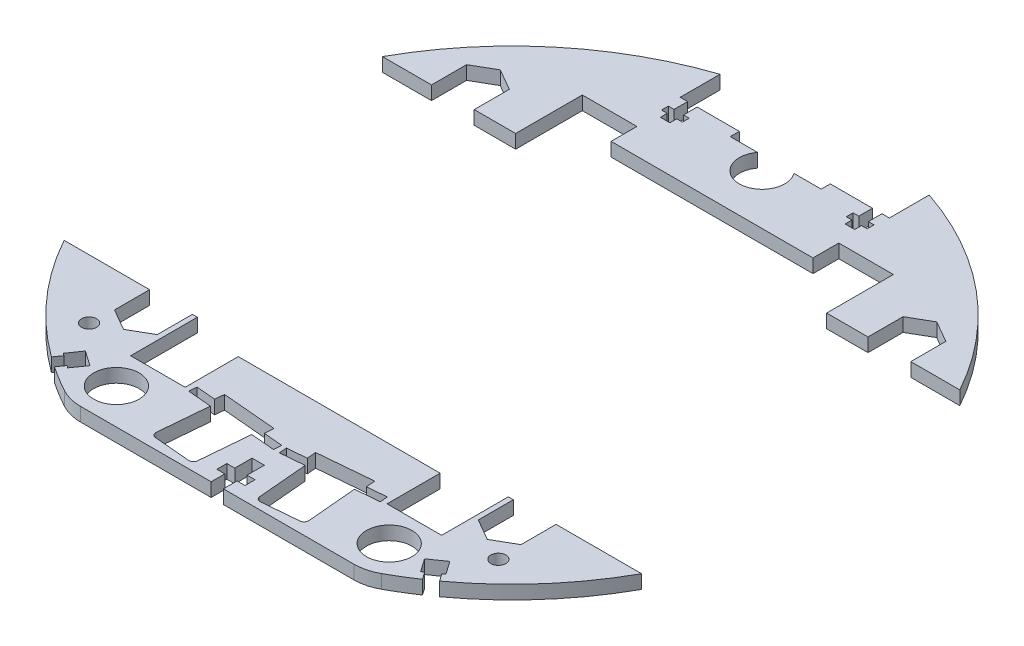
SolidWorks part; units mm, degrees
ref_plane "Front Plane" through (0, 0, 0) normal (0, 0, 1) x (1, 0, 0)
ref_plane "Top Plane" through (0, 0, 0) normal (0, 1, 0) x (1, 0, 0)
ref_plane "Right Plane" through (0, 0, 0) normal (1, 0, 0) x (0, 0, -1)
sketch "Sketch1" plane through (0, 0, 0) normal (0, 1, 0) x (1, 0, 0)
  line L0 (-30.03, -64.8129) -> (30.03, -64.8129)
  line L1 (0, -85) -> (0, 0) construction
  line L2 (0, -85) -> (32.4891, -64.8129) construction
  arc A0 (34.8348, -63.5829) -> (-34.8348, -63.5829) centre (0, 0) ccw
  circle A1 centre (0, -85) radius 38.25 construction
  arc A2 (30.03, -64.8129) -> (34.8348, -63.5829) centre (30.03, -54.8129) ccw
  arc A3 (-30.03, -64.8129) -> (-34.8348, -63.5829) centre (-30.03, -54.8129) cw
  dimension "D1" = 145
  dimension "D2" = 76.5
  dimension "D4" = 10
  dimension "D3" = 85
extrude "Boss-Extrude1" add sketch "Sketch1" along normal blind 3
sketch "Sketch2" plane through (0, 3, 0) normal (0, 1, 0) x (1, 0, 0)
  line L29 (-22.2, -49.6757) -> (-22.2, -32.5) construction
  line L30 (-22.2, -49.6757) -> (-22.2, -32.5) construction
  line L38 (-34.2, -49.6757) -> (-22.2, -49.6757) construction
  line L39 (-34.2, -49.6757) -> (-34.2, 49.6757) construction
  line L40 (-34.2, 49.6757) -> (-22.2, 49.6757) construction
  line L41 (-22.2, 32.5) -> (-22.2, 49.6757) construction
  line L47 (22.2, 32.5) -> (22.2, 49.6757) construction
  line L48 (34.2, 49.6757) -> (22.2, 49.6757) construction
  line L49 (34.2, -49.6757) -> (34.2, 49.6757) construction
  line L50 (34.2, -49.6757) -> (22.2, -49.6757) construction
  line L51 (22.2, -49.6757) -> (22.2, -32.5) construction
  line L52 (22.2, -49.6757) -> (22.2, -32.5) construction
  line L53 (-22.2, -49.6757) -> (-22.2, -38) construction
  line L54 (-22.2, -49.6757) -> (-22.2, -38)
  line L55 (-22.2, 44) -> (22.2, 44)
  line L62 (-34.2, -49.6757) -> (-22.2, -49.6757)
  line L63 (-34.2, -49.6757) -> (-34.2, 49.6757)
  line L64 (-34.2, 49.6757) -> (-22.2, 49.6757)
  line L65 (-22.2, 44) -> (-22.2, 49.6757)
  line L71 (22.2, 44) -> (22.2, 49.6757)
  line L72 (34.2, 49.6757) -> (22.2, 49.6757)
  line L73 (34.2, -49.6757) -> (34.2, 49.6757)
  line L74 (34.2, -49.6757) -> (22.2, -49.6757)
  line L75 (22.2, -49.6757) -> (22.2, -38) construction
  line L76 (22.2, -49.6757) -> (22.2, -38)
  line L77 (-22.2, -38) -> (22.2, -38)
  dimension "D1" = 38
  dimension "D2" = 44
extrude "Cut-Extrude1" cut sketch "Sketch2" against normal through all contours L54 L77 L76 L74 L73 L72 L71 L55 L65 L64 L63 L62 region at (0, 3, -1.8128)
sketch "Sketch3" plane through (0, 3, 0) normal (0, 1, 0) x (1, 0, 0)
  line L0 (-34.2, 35) -> (-34.2, -35)
  line L1 (-72.5, -35) -> (-34.2, -35)
  line L2 (-72.5, -35) -> (-72.5, 35)
  line L3 (-72.5, 35) -> (-34.2, 35)
  line L4 (72.5, -35) -> (72.5, 35)
  line L5 (-72.5, -35) -> (72.5, 35) construction
  line L6 (-72.5, 35) -> (72.5, -35) construction
  line L8 (34.2, 35) -> (34.2, -35)
  line L10 (34.2, 35) -> (72.5, 35)
  line L11 (34.2, -35) -> (72.5, -35)
  line L12 (-34.2, -49.6757) -> (-34.2, 49.6757) construction
  line L13 (34.2, -49.6757) -> (34.2, 49.6757) construction
  arc A0 (34.8348, -63.5829) -> (-34.8348, -63.5829) centre (0, 0) ccw construction
  point P0 (0, 0)
  dimension "D1" = 70
extrude "Cut-Extrude2" cut sketch "Sketch3" against normal through all
sketch "Sketch4" plane through (0, 3, 0) normal (0, 1, 0) x (1, 0, 0)
  line L0 (-21.0702, -50.0262) -> (-0.6482, -51.8129)
  line L1 (21.0702, -50.0262) -> (20.922, -48.3326)
  line L2 (0.6482, -51.8129) -> (0.5, -50.1193)
  line L3 (20.922, -48.3326) -> (0.5, -50.1193)
  line L4 (0, 0) -> (0, -64.8129) construction
  line L5 (-30.03, -64.8129) -> (30.03, -64.8129) construction
  line L6 (-20.922, -48.3326) -> (-0.5, -50.1193)
  line L7 (-0.6482, -51.8129) -> (-0.5, -50.1193)
  line L8 (-21.0702, -50.0262) -> (-20.922, -48.3326)
  line L14 (21.0702, -50.0262) -> (0.6482, -51.8129)
  dimension "D1" = 1.7
  dimension "D2" = 20.5
  dimension "D3" = 5
  dimension "D4" = 13
  dimension "D5" = 0.5
extrude "Cut-Extrude3" cut sketch "Sketch4" against normal through all
sketch "Sketch5" plane through (0, 3, 0) normal (0, 1, 0) x (1, 0, 0)
  line L0 (5.8782, -51.3553) -> (15.8401, -50.4837)
  line L1 (5.8782, -51.3553) -> (6.8369, -62.3134)
  line L2 (15.8401, -50.4837) -> (16.7988, -61.4419)
  line L3 (7.9203, -63.2225) -> (15.8898, -62.5252)
  line L4 (0.6482, -51.8129) -> (21.0702, -50.0262) construction
  line L5 (16.6882, -48.7031) -> (4.7338, -49.7489)
  line L6 (16.6882, -48.7031) -> (16.5139, -46.7107)
  line L7 (4.7338, -49.7489) -> (4.5595, -47.7565)
  line L8 (16.5139, -46.7107) -> (4.5595, -47.7565)
  line L9 (20.922, -48.3326) -> (0.5, -50.1193) construction
  line L10 (0, -38) -> (0, -64.8129) construction
  line L12 (-30.03, -64.8129) -> (30.03, -64.8129) construction
  line L13 (-16.5139, -46.7107) -> (-4.5595, -47.7565)
  line L14 (-4.7338, -49.7489) -> (-4.5595, -47.7565)
  line L15 (-16.6882, -48.7031) -> (-16.5139, -46.7107)
  line L16 (-16.6882, -48.7031) -> (-4.7338, -49.7489)
  line L17 (-7.9203, -63.2225) -> (-15.8898, -62.5252)
  line L18 (-15.8401, -50.4837) -> (-16.7988, -61.4419)
  line L19 (-5.8782, -51.3553) -> (-6.8369, -62.3134)
  line L20 (-5.8782, -51.3553) -> (-15.8401, -50.4837)
  line L21 (-22.2, -38) -> (22.2, -38) construction
  arc A0 (16.7988, -61.4419) -> (15.8898, -62.5252) centre (15.8027, -61.529) cw
  arc A1 (6.8369, -62.3134) -> (7.9203, -63.2225) centre (7.8331, -62.2263) ccw
  arc A2 (-6.8369, -62.3134) -> (-7.9203, -63.2225) centre (-7.8331, -62.2263) cw
  arc A3 (-16.7988, -61.4419) -> (-15.8898, -62.5252) centre (-15.8027, -61.529) ccw
  point P14 (10.711, -49.226)
  point P15 (10.711, -49.226)
  point P17 (10.8592, -50.9195)
  point P18 (10.8592, -50.9195)
  point P21 (16.886, -62.4381)
  point P24 (6.9241, -63.3096)
  point P40 (-6.9241, -63.3096)
  point P41 (-16.886, -62.4381)
  dimension "D5" = 1
  dimension "D1" = 12
  dimension "D2" = 10
  dimension "D3" = 12
  dimension "D4" = 2
extrude "Cut-Extrude4" cut sketch "Sketch5" against normal through all
sketch "Sketch6" plane through (0, 3, 0) normal (0, 1, 0) x (1, 0, 0)
  line L0 (0, 0) -> (0, 60) construction
  line L1 (-23, 72.5) -> (23, 72.5)
  line L2 (-23, 72.5) -> (-23, 60)
  line L3 (-23, 60) -> (-10, 60)
  line L4 (23, 72.5) -> (23, 60)
  line L5 (10, 60) -> (23, 60)
  line L7 (10, 60) -> (10, 58)
  line L8 (10, 58) -> (-10, 58)
  line L9 (-10, 60) -> (-10, 58)
  arc A1 (63.4921, 35) -> (-63.4921, 35) centre (0, 0) ccw construction
  point P14 (0, 58)
  dimension "D1" = 20
  dimension "D2" = 46
  dimension "D3" = 60
  dimension "D4" = 2
extrude "Cut-Extrude5" cut sketch "Sketch6" against normal through all
sketch "Sketch7" plane through (0, 3, 0) normal (0, 1, 0) x (1, 0, 0)
  circle A1 centre (-30, -57) radius 5
  circle A2 centre (-30, -57) radius 5
  circle A3 centre (30, -57) radius 5
  circle A4 centre (30, -57) radius 5
  dimension "D1" = 0
  dimension "D2" = 0
extrude "Cut-Extrude6" cut sketch "Sketch7" against normal through all
sketch "Sketch8" plane through (0, 3, 0) normal (0, 1, 0) x (1, 0, 0)
  line L10 (-52.7, 37.2865) -> (-52.7, 32.5)
  line L11 (-52.7, 32.5) -> (-43.3, 32.5)
  line L12 (-43.3, 32.5) -> (-43.3, 37.2865)
  line L13 (-43.3, 37.2865) -> (-43.3, 42.7135)
  line L14 (-43.3, 42.7135) -> (-48, 45.4271)
  line L15 (-48, 45.4271) -> (-52.7, 42.7135)
  line L16 (-52.7, 42.7135) -> (-52.7, 37.2865)
  line L17 (-52.7, 37.2865) -> (-52.7, 32.5)
  line L18 (-52.7, 32.5) -> (-43.3, 32.5)
  line L19 (-43.3, 32.5) -> (-43.3, 37.2865)
  line L20 (-43.3, 37.2865) -> (-43.3, 42.7135)
  line L21 (-43.3, 42.7135) -> (-48, 45.4271)
  line L22 (-48, 45.4271) -> (-52.7, 42.7135)
  line L23 (-52.7, 42.7135) -> (-52.7, 37.2865)
  line L24 (44.7, -32.5) -> (35.3, -32.5)
  line L25 (44.7, -37.2865) -> (44.7, -32.5)
  line L26 (44.7, -42.7135) -> (44.7, -37.2865)
  line L31 (40, -45.4271) -> (44.7, -42.7135)
  line L32 (35.3, -42.7135) -> (40, -45.4271)
  line L33 (35.3, -37.2865) -> (35.3, -42.7135)
  line L34 (35.3, -32.5) -> (35.3, -37.2865)
  line L35 (44.7, -32.5) -> (35.3, -32.5)
  line L36 (44.7, -37.2865) -> (44.7, -32.5)
  line L37 (44.7, -42.7135) -> (44.7, -37.2865)
  line L38 (40, -45.4271) -> (44.7, -42.7135)
  line L39 (35.3, -42.7135) -> (40, -45.4271)
  line L40 (35.3, -37.2865) -> (35.3, -42.7135)
  line L41 (35.3, -32.5) -> (35.3, -37.2865)
  line L42 (-35.3, -37.2865) -> (-35.3, -32.5)
  line L43 (-35.3, -32.5) -> (-44.7, -32.5)
  line L44 (-44.7, -32.5) -> (-44.7, -37.2865)
  line L45 (-44.7, -37.2865) -> (-44.7, -42.7135)
  line L46 (-44.7, -42.7135) -> (-40, -45.4271)
  line L47 (-40, -45.4271) -> (-35.3, -42.7135)
  line L48 (-35.3, -42.7135) -> (-35.3, -37.2865)
  line L49 (-35.3, -37.2865) -> (-35.3, -32.5)
  line L50 (-35.3, -32.5) -> (-44.7, -32.5)
  line L51 (-44.7, -32.5) -> (-44.7, -37.2865)
  line L52 (-44.7, -37.2865) -> (-44.7, -42.7135)
  line L53 (-44.7, -42.7135) -> (-40, -45.4271)
  line L54 (-40, -45.4271) -> (-35.3, -42.7135)
  line L55 (-35.3, -42.7135) -> (-35.3, -37.2865)
  line L56 (52.7, 32.5) -> (52.7, 37.2865)
  line L57 (52.7, 37.2865) -> (52.7, 42.7135)
  line L58 (52.7, 42.7135) -> (48, 45.4271)
  line L59 (48, 45.4271) -> (43.3, 42.7135)
  line L60 (43.3, 42.7135) -> (43.3, 37.2865)
  line L61 (43.3, 37.2865) -> (43.3, 32.5)
  line L62 (43.3, 32.5) -> (52.7, 32.5)
  line L63 (52.7, 32.5) -> (52.7, 37.2865)
  line L64 (52.7, 37.2865) -> (52.7, 42.7135)
  line L65 (52.7, 42.7135) -> (48, 45.4271)
  line L66 (48, 45.4271) -> (43.3, 42.7135)
  line L67 (43.3, 42.7135) -> (43.3, 37.2865)
  line L68 (43.3, 37.2865) -> (43.3, 32.5)
  line L69 (43.3, 32.5) -> (52.7, 32.5)
  dimension "D1" = 0
  dimension "D2" = 0
  dimension "D3" = 0
  dimension "D4" = 0
extrude "Cut-Extrude7" cut sketch "Sketch8" against normal through all
sketch "Sketch9" plane through (0, 3, 0) normal (0, 1, 0) x (1, 0, 0)
  line L0 (-23, 60) -> (-10, 60) construction
  line L1 (22.62, 57) -> (18.02, 57)
  line L2 (22.62, 57) -> (22.62, 55.5)
  line L3 (22.62, 55.5) -> (18.02, 55.5)
  line L4 (18.02, 57) -> (18.02, 55.5)
  line L5 (0, 0) -> (0, 44) construction
  line L6 (-22.2, 44) -> (22.2, 44) construction
  line L7 (-18.02, 57) -> (-18.02, 55.5)
  line L8 (-22.62, 55.5) -> (-18.02, 55.5)
  line L9 (-22.62, 57) -> (-22.62, 55.5)
  line L10 (-22.62, 57) -> (-18.02, 57)
  point P4 (20.32, 55.5)
  dimension "D1" = 20.32
  dimension "D2" = 1.5
  dimension "D3" = 4.6
  dimension "D4" = 3
extrude "Cut-Extrude8" cut sketch "Sketch9" against normal through all
sketch "Sketch10" plane through (0, 3, 0) normal (0, 1, 0) x (1, 0, 0)
  line L0 (22.62, 57) -> (18.02, 57) construction
  line L1 (21.37, 57) -> (19.27, 57)
  line L2 (21.37, 57) -> (21.37, 60)
  line L3 (21.37, 60) -> (19.27, 60)
  line L4 (19.27, 57) -> (19.27, 60)
  line L5 (-23, 60) -> (-10, 60) construction
  line L6 (0, 0) -> (0, 44) construction
  line L7 (-22.2, 44) -> (22.2, 44) construction
  line L8 (18.02, 55.5) -> (22.62, 55.5) construction
  line L9 (21.37, 55.5) -> (19.27, 55.5)
  line L10 (21.37, 55.5) -> (21.37, 54)
  line L11 (21.37, 54) -> (19.27, 54)
  line L12 (19.27, 55.5) -> (19.27, 54)
  line L13 (-19.27, 55.5) -> (-19.27, 54)
  line L14 (-21.37, 54) -> (-19.27, 54)
  line L15 (-21.37, 55.5) -> (-21.37, 54)
  line L16 (-21.37, 55.5) -> (-19.27, 55.5)
  line L17 (-19.27, 57) -> (-19.27, 60)
  line L18 (-21.37, 60) -> (-19.27, 60)
  line L19 (-21.37, 57) -> (-21.37, 60)
  line L20 (-21.37, 57) -> (-19.27, 57)
  point P14 (20.32, 57)
  point P16 (20.32, 57)
  dimension "D1" = 2.1
  dimension "D2" = 6
extrude "Cut-Extrude9" cut sketch "Sketch10" against normal through all
sketch "Sketch11" plane through (0, 3, 0) normal (0, 1, 0) x (1, 0, 0)
  line L0 (0, 0) -> (0, 55) construction
  circle A0 centre (0, 55) radius 5
  dimension "D2" = 10
  dimension "D1" = 55
extrude "Cut-Extrude10" cut sketch "Sketch11" against normal through all
sketch "Sketch12" plane through (0, 3, 0) normal (0, 1, 0) x (1, 0, 0)
  line L0 (-30.03, -64.8129) -> (30.03, -64.8129) construction
  line L1 (-1.35, -64.8129) -> (1.35, -64.8129)
  line L2 (-1.35, -64.8129) -> (-1.35, -61.8129)
  line L3 (-1.35, -55.8129) -> (1.35, -55.8129)
  line L4 (1.35, -64.8129) -> (1.35, -61.8129)
  line L5 (-1.35, -59.6129) -> (-3.1, -59.6129)
  line L6 (3.1, -59.6129) -> (1.35, -59.6129)
  line L7 (3.1, -59.6129) -> (3.1, -61.8129)
  line L8 (3.1, -61.8129) -> (1.35, -61.8129)
  line L9 (-3.1, -59.6129) -> (-3.1, -61.8129)
  line L10 (-1.35, -61.8129) -> (-3.1, -61.8129)
  line L11 (-1.35, -59.6129) -> (-1.35, -55.8129)
  line L12 (1.35, -59.6129) -> (1.35, -55.8129)
  point P14 (0, -64.8129)
  point P15 (0, -64.8129)
  point P16 (5.4305, -61.73)
  point P17 (0.583, -60.6034)
  dimension "D1" = 3
  dimension "D2" = 9
  dimension "D3" = 2.7
  dimension "D4" = 2.2
  dimension "D5" = 6.2
extrude "Cut-Extrude11" cut sketch "Sketch12" against normal through all
sketch "Sketch13" plane through (0, 3, 0) normal (0, 1, 0) x (1, 0, 0)
  line L0 (0, 0) -> (0, -22.8942) construction
  circle A0 centre (45, -48) radius 1.65
  circle A1 centre (-45, -48) radius 1.65
  point P5 (0, 0)
  dimension "D3" = 3.3
  dimension "D1" = 48
  dimension "D2" = 45
extrude "Cut-Extrude12" cut sketch "Sketch13" against normal through all
sketch "Sketch14" plane through (0, 0, 0) normal (0, -1, 0) x (1, 0, 0)
  line L8 (-41.543, 56.9759) -> (-42.0754, 56.6031)
  line L9 (-42.0754, 56.6031) -> (-40.0679, 53.736)
  line L10 (-40.0679, 53.736) -> (-36.7913, 56.0303)
  line L11 (-36.7913, 56.0303) -> (-38.7988, 58.8974)
  line L12 (-38.7988, 58.8974) -> (-39.3313, 58.5245)
  line L13 (-39.3313, 58.5245) -> (-40.4784, 60.1629)
  line L14 (-40.4784, 60.1629) -> (-42.6901, 58.6142)
  line L15 (-42.6901, 58.6142) -> (-41.543, 56.9759)
  line L16 (-41.543, 56.9759) -> (-42.0754, 56.6031)
  line L17 (-42.0754, 56.6031) -> (-40.0679, 53.736)
  line L18 (-40.0679, 53.736) -> (-36.7913, 56.0303)
  line L19 (-36.7913, 56.0303) -> (-38.7988, 58.8974)
  line L20 (-38.7988, 58.8974) -> (-39.3313, 58.5245)
  line L21 (-39.3313, 58.5245) -> (-40.4784, 60.1629)
  line L22 (-40.4784, 60.1629) -> (-42.6901, 58.6142)
  line L23 (-42.6901, 58.6142) -> (-41.543, 56.9759)
  line L24 (41.543, 56.9759) -> (42.6901, 58.6142)
  line L25 (42.0754, 56.6031) -> (41.543, 56.9759)
  line L26 (40.0679, 53.736) -> (42.0754, 56.6031)
  line L27 (36.7913, 56.0303) -> (40.0679, 53.736)
  line L28 (38.7988, 58.8974) -> (36.7913, 56.0303)
  line L29 (39.3313, 58.5245) -> (38.7988, 58.8974)
  line L30 (40.4784, 60.1629) -> (39.3313, 58.5245)
  line L31 (42.6901, 58.6142) -> (40.4784, 60.1629)
  line L32 (41.543, 56.9759) -> (42.6901, 58.6142)
  line L33 (42.0754, 56.6031) -> (41.543, 56.9759)
  line L34 (40.0679, 53.736) -> (42.0754, 56.6031)
  line L35 (36.7913, 56.0303) -> (40.0679, 53.736)
  line L36 (38.7988, 58.8974) -> (36.7913, 56.0303)
  line L37 (39.3313, 58.5245) -> (38.7988, 58.8974)
  line L38 (40.4784, 60.1629) -> (39.3313, 58.5245)
  line L39 (42.6901, 58.6142) -> (40.4784, 60.1629)
  dimension "D1" = 0
  dimension "D2" = 0
extrude "Cut-Extrude13" cut sketch "Sketch14" against normal through all
equation "\"smallPulleyTeeth\"= 30"
equation "\"largePulleyTeeth\"= 30"
equation "\"eighthThick\"= 3.0mm"
equation "\"sixteenthThick\" = 1.7mm"
equation "\"quarterThick\"=6.0mm"
equation "\"OD\" = 145mm"
equation "\"puckAngle\" = 60.5deg"
equation "\"puckDiam\" = 76.5mm"
equation "\"axlePress\" = 5.9mm"
equation "\"press\" = 0.2mm"
equation "\"wheelClear\" = 0.3mm"
equation "\"10-32clear\" = 4.8mm"
equation "\"6-32clear\" = 3.3mm"
equation "\"8-32clear\" = 4.0mm"
equation "\"4-40clear\" = 3.0mm"
equation "\"wheelHeight\" = 22mm"
equation "\"wheelWell\" = 65mm"
equation "\"D1@Sketch1\"=\"OD\""
equation "\"D1@Boss-Extrude1\"=\"eighthThick\""
equation "\"D2@Sketch1\"=\"puckDiam\""
equation "\"puckDist\" = 85mm"
equation "\"scoopFillet\" = 5mm"
equation "\"10-32tap\" = 4.45mm"
equation "\"ledSmall\" = 3.1mm"
equation "\"ledLarge\" = 4.2mm"
equation "\"ledLength\" = 4.2mm"
equation "\"D3@Sketch1\"=\"puckDist\""
equation "\"4-40close\" = 2.7mm"
equation "\"4-40nutThick\" = 2.2mm"
equation "\"4-40nutWidth\" = 6.2mm"
equation "\"D3@Sketch12\"=\"4-40close\""
equation "\"D4@Sketch12\"=\"4-40nutThick\""
equation "\"D5@Sketch12\"=\"4-40nutWidth\""
equation "\"D3@Sketch13\"=\"6-32clear\""
